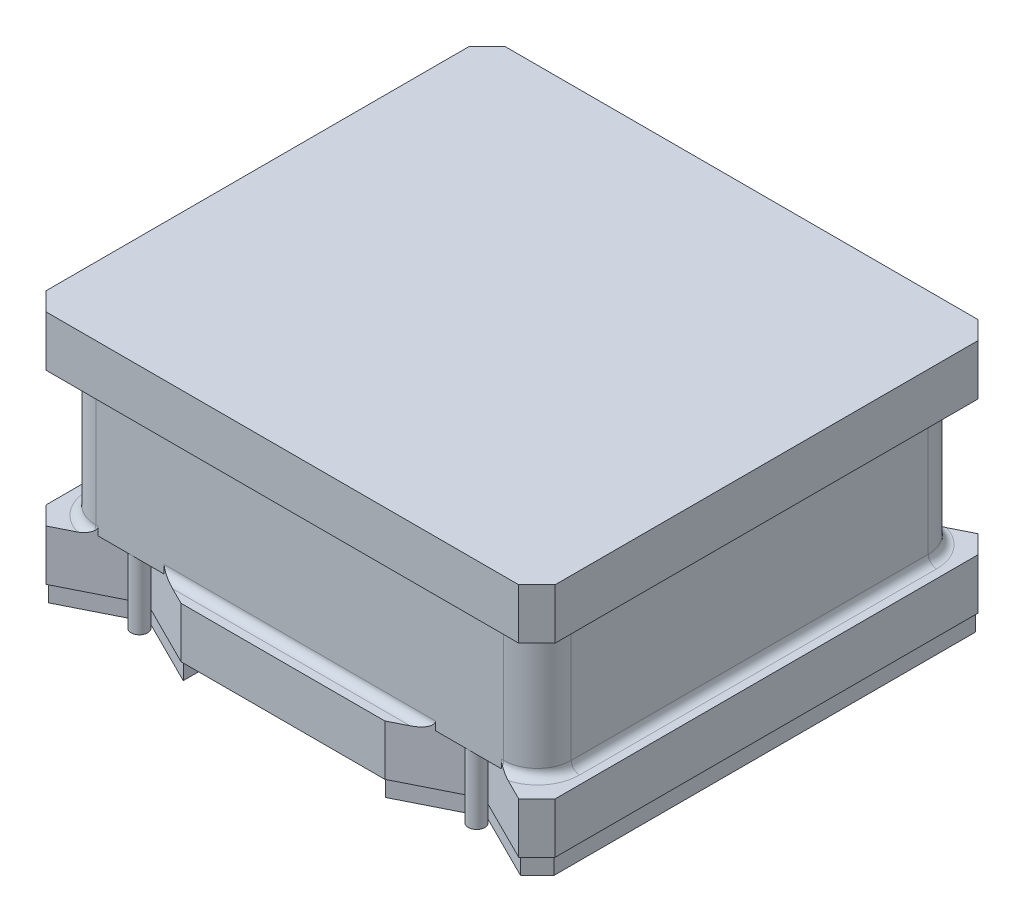
SolidWorks part; units mm, degrees
ref_plane "Plano frontal" through (0, 0, 0) normal (0, 0, 1) x (1, 0, 0)
ref_plane "Plano superior" through (0, 0, 0) normal (0, 1, 0) x (1, 0, 0)
ref_plane "Plano direito" through (0, 0, 0) normal (1, 0, 0) x (0, 0, -1)
sketch "Esboço1" plane through (0, 0, 0) normal (0, 1, 0) x (1, 0, 0)
  line L0 (-1.5, 0) -> (1.945, 0) construction
  line L1 (-1.5, 1.25) -> (-1.5, -1.25)
  line L2 (-1.4, 1.35) -> (-0.6, 1.35) construction
  line L3 (-0.6, -1.35) -> (-0.6, 1.35)
  line L4 (-1, -1.35) -> (-1, -1.15) construction
  line L5 (-1.4, 1.35) -> (-1.5, 1.25)
  line L6 (-1.4, -1.35) -> (-0.6, -1.35) construction
  line L7 (-1, 1.35) -> (-1, 1.15) construction
  line L8 (-1.4, 1.35) -> (-1, 1.15)
  line L9 (-1, 1.15) -> (-0.6, 1.35)
  line L10 (-1, -1.15) -> (-0.6, -1.35)
  line L11 (-1.4, -1.35) -> (-1, -1.15)
  line L12 (-1.4, -1.35) -> (-1.5, -1.25)
  line L13 (0, 1.35) -> (0, -1.35) construction
  line L14 (1, 1.35) -> (1, 1.15) construction
  line L15 (1.4, -1.35) -> (0.6, -1.35) construction
  line L16 (1, -1.35) -> (1, -1.15) construction
  line L17 (1.4, 1.35) -> (0.6, 1.35) construction
  line L18 (1.4, -1.35) -> (1.5, -1.25)
  line L19 (1.4, -1.35) -> (1, -1.15)
  line L20 (1, -1.15) -> (0.6, -1.35)
  line L21 (1, 1.15) -> (0.6, 1.35)
  line L22 (1.4, 1.35) -> (1, 1.15)
  line L23 (1.4, 1.35) -> (1.5, 1.25)
  line L24 (0.6, -1.35) -> (0.6, 1.35)
  line L25 (1.5, 1.25) -> (1.5, -1.25)
  point P3 (-1.5, 1.35)
  point P13 (-1.5, -1.35)
  point P15 (-0.6, 0)
  point P28 (0.6, 0)
  point P29 (1.5, -1.35)
  point P30 (1.5, 1.35)
  dimension "D1" = 1.35
  dimension "D2" = 0.9
  dimension "D3" = 0.6
  dimension "D5" = 135
  dimension "D4" = 0.2
  dimension "D6" = 0.9
extrude "Ressalto-extrusão1" add sketch "Esboço1" along normal blind 0.1
sketch "Esboço2" plane through (0, 0.1, 0) normal (0, 1, 0) x (1, 0, 0)
  line L7 (1.4, 1.35) -> (1, 1.15) construction
  line L10 (1, 1.15) -> (0.6, 1.35) construction
  line L16 (1.5, 1.25) -> (1.4, 1.35) construction
  line L17 (1.5, -1.25) -> (1.5, 1.25) construction
  line L18 (1.4, -1.35) -> (1.5, -1.25) construction
  line L19 (1, -1.15) -> (1.4, -1.35) construction
  line L20 (0.6, -1.35) -> (1, -1.15) construction
  line L21 (-1, -1.15) -> (-0.6, -1.35) construction
  line L22 (-1.4, -1.35) -> (-1, -1.15) construction
  line L23 (-1.5, -1.25) -> (-1.4, -1.35) construction
  line L24 (-1.5, 1.25) -> (-1.5, -1.25) construction
  line L25 (-0.6, 1.35) -> (-1, 1.15) construction
  line L26 (-1, 1.15) -> (-1.4, 1.35) construction
  line L27 (-1.4, 1.35) -> (-1.5, 1.25) construction
  line L120 (-1.4, 1.35) -> (-1.5, 1.25)
  line L121 (-1, 1.15) -> (-1.4, 1.35)
  line L122 (-0.6, 1.35) -> (-1, 1.15)
  line L123 (-1.5, 1.25) -> (-1.5, -1.25)
  line L124 (-1.5, -1.25) -> (-1.4, -1.35)
  line L125 (-1.4, -1.35) -> (-1, -1.15)
  line L126 (-1, -1.15) -> (-0.6, -1.35)
  line L127 (0.6, -1.35) -> (1, -1.15)
  line L128 (1, -1.15) -> (1.4, -1.35)
  line L129 (1.4, -1.35) -> (1.5, -1.25)
  line L130 (1.5, -1.25) -> (1.5, 1.25)
  line L131 (1.5, 1.25) -> (1.4, 1.35)
  line L132 (1, 1.15) -> (0.6, 1.35)
  line L133 (1.4, 1.35) -> (1, 1.15)
  line L134 (-0.6045, 1.3589) -> (-1, 1.1612)
  line L135 (-1, 1.1612) -> (-1.402, 1.3622)
  line L136 (-1.402, 1.3622) -> (-1.51, 1.2541)
  line L137 (-1.51, 1.2541) -> (-1.51, -1.2541)
  line L138 (-1.51, -1.2541) -> (-1.402, -1.3622)
  line L139 (-1.402, -1.3622) -> (-1, -1.1612)
  line L140 (-1, -1.1612) -> (-0.6045, -1.3589)
  line L141 (0.6045, -1.3589) -> (1, -1.1612)
  line L142 (1, -1.1612) -> (1.402, -1.3622)
  line L143 (1.402, -1.3622) -> (1.51, -1.2541)
  line L144 (1.51, -1.2541) -> (1.51, 1.2541)
  line L145 (1.51, 1.2541) -> (1.402, 1.3622)
  line L146 (1.402, 1.3622) -> (1, 1.1612)
  line L147 (1, 1.1612) -> (0.6045, 1.3589)
  line L148 (-0.6045, 1.3589) -> (0.6045, 1.3589)
  line L149 (-0.6045, -1.3589) -> (0.6045, -1.3589)
  dimension "D1" = 0.01
extrude "Ressalto-extrusão2" add sketch "Esboço2" along normal blind 0.3
sketch "Esboço3" plane through (0, 0.4, 0) normal (0, 1, 0) x (1, 0, 0)
  line L0 (-0.6045, 1.3589) -> (0.6045, 1.3589) construction
  line L1 (-1.41, 1.2589) -> (1.41, 1.2589)
  line L2 (-1.41, 1.2589) -> (-1.41, -1.2589)
  line L3 (-1.41, -1.2589) -> (1.41, -1.2589)
  line L4 (1.41, 1.2589) -> (1.41, -1.2589)
  line L5 (-1.41, 1.2589) -> (1.41, -1.2589) construction
  line L6 (-1.41, -1.2589) -> (1.41, 1.2589) construction
  line L7 (1.51, -1.2541) -> (1.51, 1.2541) construction
  point P0 (0, 0)
  dimension "D1" = 0.1
  dimension "D2" = 0.1
extrude "Ressalto-extrusão3" add sketch "Esboço3" along normal blind 0.8
sketch "Esboço4" plane through (0, 1.2, 0) normal (0, 1, 0) x (1, 0, 0)
  line L0 (-1.51, 1.2541) -> (-1.402, 1.3622)
  line L1 (-1.402, 1.3622) -> (1.402, 1.3622)
  line L2 (1.402, 1.3622) -> (1.51, 1.2541)
  line L3 (1.51, 1.2541) -> (1.51, -1.2541)
  line L4 (1.51, -1.2541) -> (1.402, -1.3622)
  line L5 (1.402, -1.3622) -> (-1.402, -1.3622)
  line L6 (-1.402, -1.3622) -> (-1.51, -1.2541)
  line L7 (-1.51, -1.2541) -> (-1.51, 1.2541)
extrude "Ressalto-extrusão4" add sketch "Esboço4" along normal blind 0.3
fillet "Filete1" radius 0.2 4 edges at (-1.41, 0.8, -1.2589) (1.41, 0.8, -1.2589) (1.41, 0.8, 1.2589) (-1.41, 0.8, 1.2589)
fillet "Filete2" radius 0.05 8 edges at (1.3514, 1.2, -1.2004) (1.41, 1.2, 0) (1.3514, 1.2, 1.2004) (0, 1.2, 1.2589) (-1.3514, 1.2, 1.2004) (-1.41, 1.2, 0) (-1.3514, 1.2, -1.2004) (0, 1.2, -1.2589)
fillet "Filete3" radius 0.05 12 edges at (-1.2028, 0.4, 1.2589) (-1.3514, 0.4, 1.2004) (-1.41, 0.4, 0) (-1.2028, 0.4, -1.2589) (1.2028, 0.4, 1.2589) (1.3514, 0.4, 1.2004) (1.2028, 0.4, -1.2589) (1.3514, 0.4, -1.2004) (-1.3514, 0.4, -1.2004) (0, 0.4, -1.2589) (1.41, 0.4, 0) (0, 0.4, 1.2589)
sketch "Esboço5" plane through (0, 0.4, 0) normal (0, -1, 0) x (1, 0, 0)
  line L0 (-1, 1.1612) -> (-1, 1.2589) construction
  line L1 (-1.1955, 1.2589) -> (-0.8045, 1.2589) construction
  line L2 (0, 0) -> (0, 1.3589) construction
  line L3 (-0.6045, 1.3589) -> (0.6045, 1.3589) construction
  circle A0 centre (-1, 1.2101) radius 0.0489
  circle A1 centre (1, 1.2101) radius 0.0489
extrude "Ressalto-extrusão5" add sketch "Esboço5" along normal up to surface (0.4 mm away) up to face at (-1.125, 0, 0)
